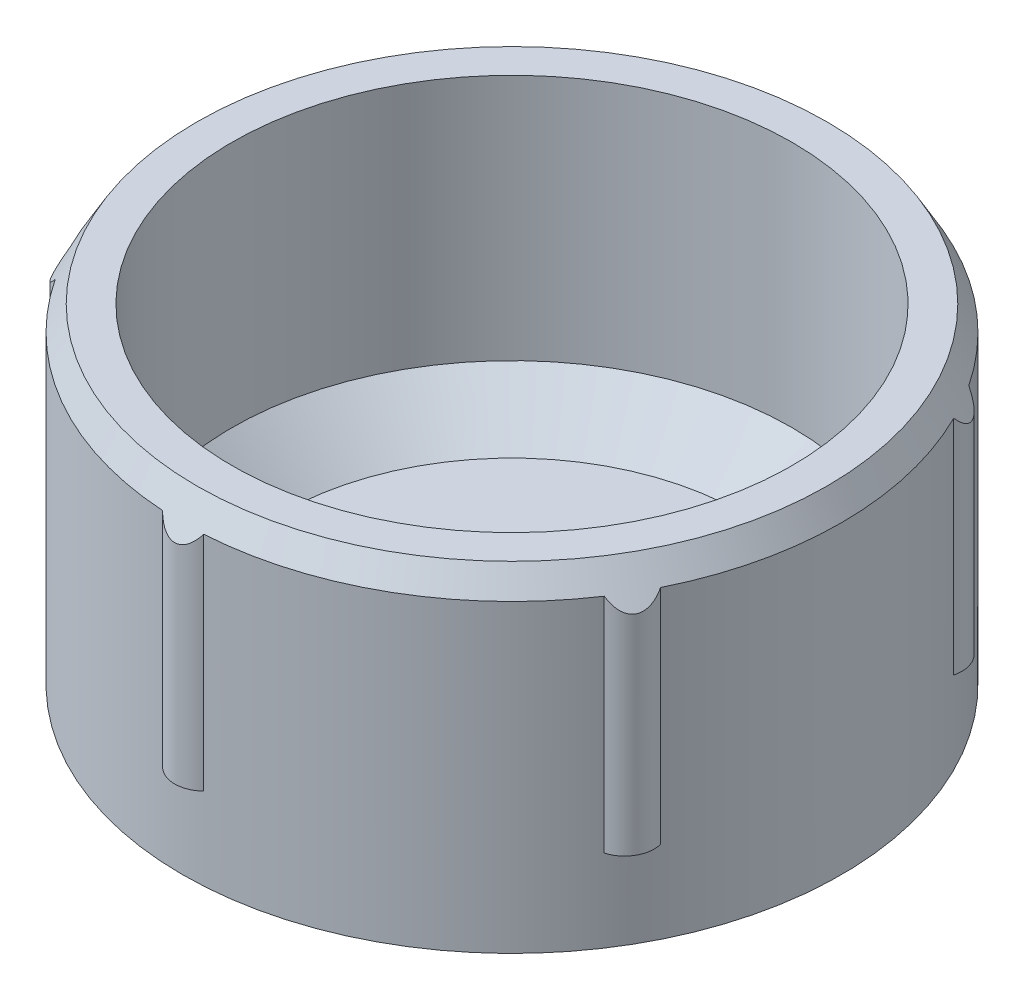
SolidWorks part; units mm, degrees
material "PET"
ref_plane "Front Plane" through (0, 0, 0) normal (0, 0, 1) x (1, 0, 0)
ref_plane "Top Plane" through (0, 0, 0) normal (0, 1, 0) x (1, 0, 0)
ref_plane "Right Plane" through (0, 0, 0) normal (1, 0, 0) x (0, 0, -1)
sketch "Sketch2" plane through (0, 0, 0) normal (0, 0, 1) x (1, 0, 0)
  line L0 (0, 0) -> (-20, 0)
  line L1 (-20, 0) -> (-20, 20)
  line L2 (-20, 20) -> (-17, 20)
  line L3 (-17, 20) -> (-17, 2)
  line L4 (-17, 2) -> (0, 2)
  line L5 (0, 2) -> (0, 0)
  line L6 (0, 0) -> (0, 22119.0408) construction
  dimension "D1" = 40
  dimension "D2" = 3
  dimension "D3" = 20
  dimension "D4" = 2
revolve "Revolve1" add sketch "Sketch2" angle 360 about L6
sketch "Sketch3" plane through (0, 20, 0) normal (0, 1, 0) x (1, 0, 0)
  arc A0 (-1.25, 19.9609) -> (1.25, 19.9609) centre (0, 18.6809) cw
  circle A1 centre (0, 0) radius 20 construction
  arc A2 (-1.25, 19.9609) -> (1.25, 19.9609) centre (0, 0) cw
  arc A3 (16.6616, 11.063) -> (17.9116, 8.8979) centre (0, 0) cw
  arc A4 (16.6616, 11.063) -> (17.9116, 8.8979) centre (16.1781, 9.3404) cw
  arc A5 (17.9116, -8.8979) -> (16.6616, -11.063) centre (0, 0) cw
  arc A6 (17.9116, -8.8979) -> (16.6616, -11.063) centre (16.1781, -9.3404) cw
  arc A7 (1.25, -19.9609) -> (-1.25, -19.9609) centre (0, 0) cw
  arc A8 (1.25, -19.9609) -> (-1.25, -19.9609) centre (0, -18.6809) cw
  arc A9 (-16.6616, -11.063) -> (-17.9116, -8.8979) centre (0, 0) cw
  arc A10 (-16.6616, -11.063) -> (-17.9116, -8.8979) centre (-16.1781, -9.3404) cw
  arc A11 (-17.9116, 8.8979) -> (-16.6616, 11.063) centre (0, 0) cw
  arc A12 (-17.9116, 8.8979) -> (-16.6616, 11.063) centre (-16.1781, 9.3404) cw
  point P24 (0, 0)
  dimension "D1" = 2.5
  dimension "D2" = 20.47
extrude "Boss-Extrude1" add sketch "Sketch3" against normal offset from surface (15 mm away) 5 up to face at (0, 0, -20)
ref_axis "Axis1" through (0, 20, 0) along (0, -1, 0)
sketch "Sketch4" plane through (0, 0, 0) normal (0, 0, 1) x (1, 0, 0)
  line L0 (-21, 16.7679) -> (-18.5566, 21)
  line L1 (-18.5566, 21) -> (-21, 21)
  line L2 (-21, 21) -> (-21, 16.7679)
  point P2 (-20, 20)
  dimension "D1" = 1
  dimension "D2" = 1
  dimension "D3" = 0.75
  dimension "D4" = 30
revolve "Cut-Revolve1" cut sketch "Sketch4" angle 360 about axis through (0, 20, 0) along (0, -1, 0)
sketch "Sketch5" plane through (0, 2, 0) normal (0, 1, 0) x (1, 0, 0)
  circle A0 centre (0, 9.5) radius 1.7
  circle A1 centre (8.2272, -4.75) radius 1.7
  circle A2 centre (-8.2272, -4.75) radius 1.7
  point P10 (0, 0)
  dimension "D3" = 3.4
  dimension "D1" = 9.5
  dimension "D2" = 3
extrude "Cut-Extrude1" cut sketch "Sketch5" against normal up to next
chamfer "Chamfer1" distance 3 angle 45 1 edges at (0, 2, -17)
equation "\"D2@Sketch3\"=(1.6in/2)+0.15mm"
